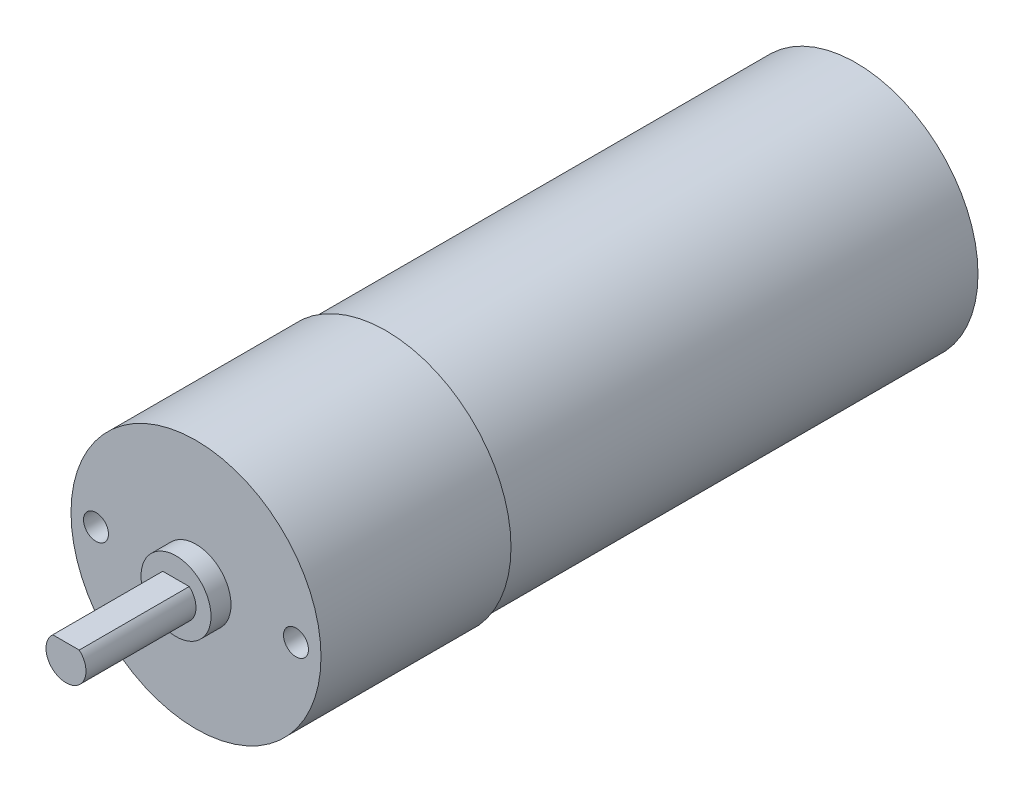
SolidWorks part; units mm, degrees
ref_plane "Front Plane" through (0, 0, 0) normal (0, 0, 1) x (1, 0, 0)
ref_plane "Top Plane" through (0, 0, 0) normal (0, 1, 0) x (1, 0, 0)
ref_plane "Right Plane" through (0, 0, 0) normal (1, 0, 0) x (0, 0, -1)
sketch "Sketch1" plane through (0, 0, 0) normal (0, 0, 1) x (1, 0, 0)
  circle A0 centre (0, 0) radius 12.2
  circle A1 centre (0, 0) radius 12.5
  dimension "D1" = 24.4
  dimension "D2" = 25
extrude "Boss-Extrude1" add sketch "Sketch1" along normal blind 47 contours A0 region at (0, 0, 0)
extrude "Boss-Extrude2" add sketch "Sketch1<3>" along normal blind 19 from surface contours A0 | A1 A0 region at (0, 0, 0) region at (-12.4646, 0, 0) starting at face at (12.2, 0, 47)
sketch "Sketch1<3>" plane through (0, 0, 0) normal (0, 0, 1) x (1, 0, 0) same geometry as "Sketch1"
sketch "Sketch2" plane through (0, 0, 66) normal (0, 0, 1) x (1, 0, 0)
  line L0 (-1.3229, 1.5) -> (1.3229, 1.5)
  circle A0 centre (0, 0) radius 3.5
  circle A1 centre (0, 0) radius 2
  dimension "D1" = 7
  dimension "D2" = 4
  dimension "D3" = 0.5
extrude "Boss-Extrude4" add sketch "Sketch2" along normal blind 2 contours L0 A1 | L0 A1 | A0 A1 region at (0, 1.7023, 66) region at (0, -0.1324, 66) region at (-3.401, 0, 66)
extrude "Boss-Extrude5" add sketch "Sketch2<4>" along normal blind 11 from surface contours L0 A1 region at (0, -0.1324, 66) starting at face at (3.5, 0, 68)
sketch "Sketch2<4>" plane through (0, 0, 66) normal (0, 0, 1) x (1, 0, 0) same geometry as "Sketch2"
sketch "Sketch3" plane through (0, 0, 66) normal (0, 0, 1) x (1, 0, 0)
  line L0 (0, 12.5) -> (0, -12.5) construction
  circle A0 centre (0, 0) radius 12.5 construction
  circle A1 centre (10, 0) radius 1.5
  circle A2 centre (-10, 0) radius 1.5
  dimension "D1" = 3
  dimension "D2" = 10
hole_wizard "M3x0.5 Tapped Hole1" positions "3DSketch1" profile "Sketch4" tap size "M3x0.5" standard "ANSI Metric"
sketch3d "3DSketch1"
  point P0 (-10, 0, 66)
  point P3 (10, 0, 66)
sketch "Sketch4" plane through (-10, 0, 66) normal (1, 0, 0) x (0, -1, 0)
  line L0 (0, 0) -> (0, 8.2511)
  line L1 (0, 8.2511) -> (1.25, 7.5)
  line L2 (1.25, 7.5) -> (1.25, 0)
  line L5 (1.25, 0) -> (0, 0)
  line L10 (0, 8.2511) -> (-1.25, 7.5) construction
  line L11 (0, -6.35) -> (0, 107.95) construction
  dimension "Tap Drill Dia." = 2.5
  dimension "Tap Drill Depth" = 7.5
  dimension "Drill Angle" = 118
